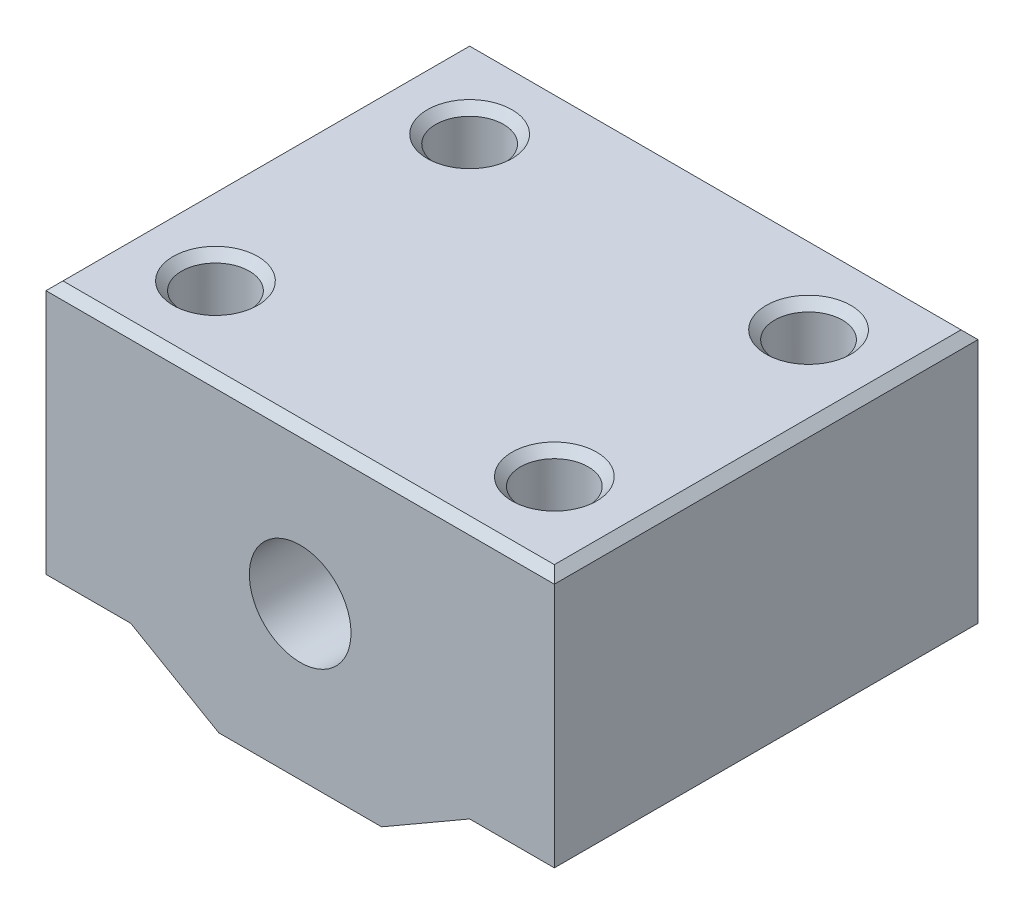
SolidWorks part; units mm, degrees
ref_plane "정면" through (0, 0, 0) normal (0, 0, 1) x (1, 0, 0)
ref_plane "윗면" through (0, 0, 0) normal (0, 1, 0) x (1, 0, 0)
ref_plane "우측면" through (0, 0, 0) normal (1, 0, 0) x (0, 0, -1)
sketch "스케치1" plane through (0, 0, 0) normal (0, 0, 1) x (1, 0, 0)
  line L0 (0, 7.5) -> (0, -7.5) construction
  line L1 (-15, -7.5) -> (-10, -7.5)
  line L2 (-15, -7.5) -> (-15, 7.5)
  line L3 (-15, 7.5) -> (15, 7.5)
  line L4 (15, -7.5) -> (15, 7.5)
  line L5 (-15, -7.5) -> (15, 7.5) construction
  line L6 (-15, 7.5) -> (15, -7.5) construction
  line L7 (-10, -7.5) -> (-4.8038, -10.5)
  line L8 (10, -7.5) -> (4.8038, -10.5)
  line L9 (-4.8038, -10.5) -> (4.8038, -10.5)
  line L10 (10, -7.5) -> (15, -7.5)
  point P0 (0, 0)
  point P13 (0, -10.5)
  dimension "D1" = 30
  dimension "D2" = 15
  dimension "D3" = 3
  dimension "D4" = 20
  dimension "D5" = 30
extrude "보스-돌출1" add sketch "스케치1" along normal blind 25
sketch "스케치2" plane through (0, 7.5, 0) normal (0, 1, 0) x (1, 0, 0)
  line L0 (0, 0) -> (0, -25) construction
  line L1 (-10, 0) -> (-10, -25) construction
  line L2 (10, 0) -> (10, -25) construction
  line L3 (-15, -12.5) -> (15, -12.5) construction
  line L4 (15, 0) -> (-15, 0)
  line L5 (-15, 0) -> (-15, -25)
  line L6 (-15, -25) -> (15, -25)
  line L7 (15, -25) -> (15, 0)
  line L8 (15, 0) -> (-15, 0)
  line L9 (-15, 0) -> (-15, -25)
  line L10 (-15, -25) -> (15, -25)
  line L11 (15, -25) -> (15, 0)
  circle A0 centre (-10, -5) radius 2
  circle A1 centre (10, -5) radius 2
  circle A2 centre (-10, -20) radius 2
  circle A3 centre (10, -20) radius 2
  point P20 (-10, -12.5)
  dimension "D2" = 4
  dimension "D3" = 15
  dimension "D4" = 5
  dimension "D1" = 0
extrude "컷-돌출1" cut sketch "스케치2" against normal through all contours A0 | A2 | A3 | A1 region at (-10, 7.5, 5) region at (10, 7.5, 5) region at (-10, 7.5, 20) region at (10, 7.5, 20)
sketch "스케치3" plane through (0, 0, 25) normal (0, 0, 1) x (1, 0, 0)
  line L0 (0, 7.5) -> (0, -10.5) construction
  line L1 (15, 7.5) -> (-15, 7.5) construction
  line L2 (-4.8038, -10.5) -> (4.8038, -10.5) construction
  circle A0 centre (0, -1.5) radius 3
  dimension "D1" = 6
  dimension "D2" = 9
extrude "컷-돌출2" cut sketch "스케치3" against normal through all
chamfer "모따기1" distance 0.5 angle 45 8 edges at (15, 7.5, 12.5) (0, 7.5, 25) (-15, 7.5, 12.5) (0, 7.5, 0) (-10, 7.5, 7) (-10, 7.5, 22) (10, 7.5, 22) (10, 7.5, 7)
